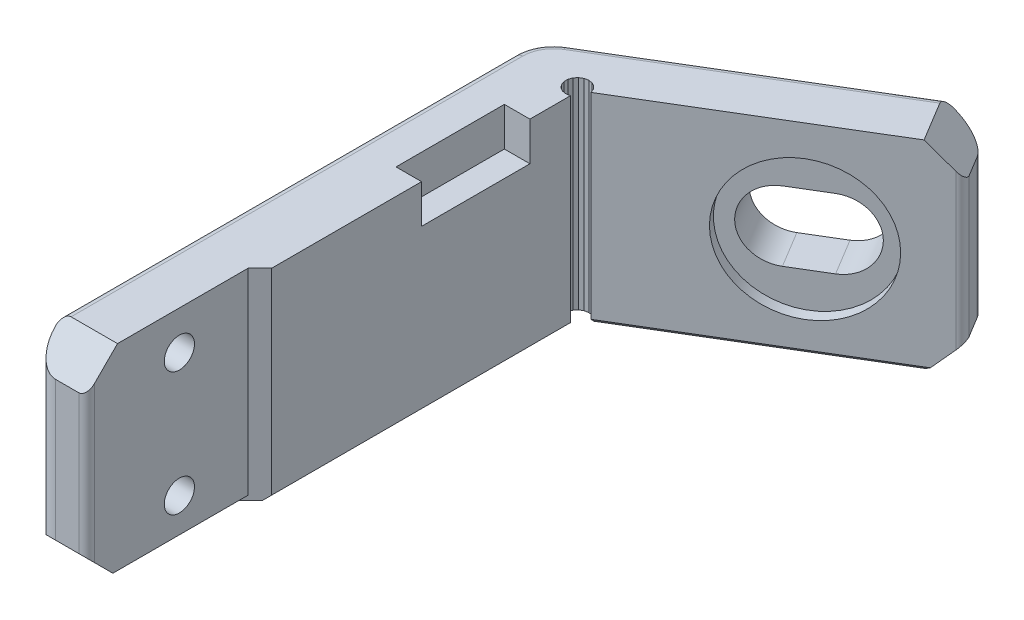
SolidWorks part; units mm, degrees
ref_plane "Front Plane" through (0, 0, 0) normal (0, 0, 1) x (1, 0, 0)
ref_plane "Top Plane" through (0, 0, 0) normal (0, 1, 0) x (1, 0, 0)
ref_plane "Right Plane" through (0, 0, 0) normal (1, 0, 0) x (0, 0, -1)
ref_plane "PY -20.700" through (0, -20.7, 0) normal (0, 1, 0) x (1, 0, 0)
sketch "leg and pad sketch" plane through (0, -20.7, 0) normal (0, 1, 0) x (1, 0, 0)
  line L0 (0.5513, 30.3327) -> (0.3673, 30.8194)
  line L1 (0.3673, 30.8194) -> (0.028, 31.2139)
  line L2 (0.028, 31.2139) -> (-0.4256, 31.4688)
  line L3 (-0.4256, 31.4688) -> (-0.939, 31.5534)
  line L4 (-0.939, 31.5534) -> (-1.4504, 31.4576)
  line L5 (-1.4504, 31.4576) -> (-1.8983, 31.1928)
  line L6 (-1.8983, 31.1928) -> (-2.2288, 30.7909)
  line L7 (-2.2288, 30.7909) -> (-2.4021, 30.3003)
  line L8 (-2.4021, 30.3003) -> (-2.3973, 29.78)
  line L9 (-2.3973, 29.78) -> (-2.2152, 29.2926)
  line L10 (-2.2152, 29.2926) -> (-1.8775, 28.8968)
  line L11 (-1.8775, 28.8968) -> (-1.4248, 28.6402)
  line L12 (-1.4248, 28.6402) -> (-0.9118, 28.5536)
  line L13 (-0.9118, 28.5536) -> (-0.4, 28.6475)
  line L14 (-0.4, 28.6475) -> (-0.4, -9.98)
  line L15 (-0.4, -9.98) -> (-1.92, -11.5)
  line L16 (-1.92, -11.5) -> (-1.92, -32.37)
  line L17 (-1.92, -32.37) -> (-8.92, -32.37)
  line L18 (-8.92, -32.37) -> (-8.92, 32.7926)
  line L19 (-8.92, 32.7926) -> (27.2048, 54.5947)
  line L20 (27.2048, 54.5947) -> (30.8218, 48.6015)
  line L21 (30.8218, 48.6015) -> (0.5513, 30.3327)
extrude "leg and pad" add sketch "leg and pad sketch" along normal mid plane 26
ref_plane "PX -1.350" through (-1.35, 0, 0) normal (1, 0, 0) x (0, 0, -1)
sketch "screw head relief sketch" plane through (-1.35, 0, 0) normal (1, 0, 0) x (0, 0, -1)
  line L0 (23.4, -12.7) -> (23.4, -6.7)
  line L1 (23.4, -6.7) -> (9.4, -6.7)
  line L2 (9.4, -6.7) -> (9.4, -12.7)
  line L3 (9.4, -12.7) -> (23.4, -12.7)
extrude "screw head relief" cut sketch "screw head relief sketch" against normal mid plane 4.7
sketch "insert flange relief sketch" plane through (0, -20.7, 0) normal (0, 1, 0) x (1, 0, 0)
  line L0 (18.3249, 39.8914) -> (17.0331, 42.0318)
  line L1 (17.0331, 42.0318) -> (9.3276, 37.3814)
  line L2 (9.3276, 37.3814) -> (10.6194, 35.241)
  line L3 (10.6194, 35.241) -> (18.3249, 39.8914)
revolve "insert flange relief" cut sketch "insert flange relief sketch" angle 360 about L0
sketch "M6 slot end 1 sketch" plane through (0, -20.7, 0) normal (0, 1, 0) x (1, 0, 0)
  line L0 (20.4653, 41.1832) -> (15.8149, 48.8886)
  line L1 (15.8149, 48.8886) -> (11.9621, 46.5634)
  line L2 (11.9621, 46.5634) -> (16.6125, 38.858)
  line L3 (16.6125, 38.858) -> (20.4653, 41.1832)
revolve "M6 slot end 1" cut sketch "M6 slot end 1 sketch" angle 360 about L0
sketch "M6 slot end 2 sketch" plane through (0, -20.7, 0) normal (0, 1, 0) x (1, 0, 0)
  line L0 (16.1845, 38.5996) -> (11.5341, 46.3051)
  line L1 (11.5341, 46.3051) -> (7.6813, 43.9799)
  line L2 (7.6813, 43.9799) -> (12.3317, 36.2744)
  line L3 (12.3317, 36.2744) -> (16.1845, 38.5996)
revolve "M6 slot end 2" cut sketch "M6 slot end 2 sketch" angle 360 about L0
sketch "M6 slot middle sketch" plane through (0, -20.7, 0) normal (0, 1, 0) x (1, 0, 0)
  line L0 (16.1845, 38.5996) -> (20.4653, 41.1832)
  line L1 (20.4653, 41.1832) -> (15.8149, 48.8886)
  line L2 (15.8149, 48.8886) -> (11.5341, 46.3051)
  line L3 (11.5341, 46.3051) -> (16.1845, 38.5996)
extrude "M6 slot middle" cut sketch "M6 slot middle sketch" against normal mid plane 9
ref_plane "PX -5.420" through (-5.42, 0, 0) normal (1, 0, 0) x (0, 0, -1)
sketch "screw holes sketch" plane through (-5.42, 0, 0) normal (1, 0, 0) x (0, 0, -1)
  circle A0 centre (-20.375, -28.7) radius 1.95
  circle A1 centre (-20.375, -12.7) radius 1.95
extrude "screw holes" cut sketch "screw holes sketch" against normal mid plane 9
chamfer "leg top corners" distance 4 angle 45 2 edges at (-5.42, -7.7, 32.37) (-5.42, -33.7, 32.37) tangent propagation no
chamfer "pad end corners" distance 4 angle 45 2 edges at (29.0133, -7.7, -51.5981) (29.0133, -33.7, -51.5981) tangent propagation no
fillet "outside of the bend" radius 5 1 edges at (-8.92, -20.7, -32.7926) tangent propagation no
fillet "leg top outer edge" radius 3 1 edges at (-8.92, -20.7, 32.37) tangent propagation no
fillet "pad end outer edge" radius 3 1 edges at (27.2048, -20.7, -54.5947) tangent propagation no
fillet "leg top inner edge" radius 1 1 edges at (-1.92, -20.7, 32.37) tangent propagation no
fillet "pad end inner edge" radius 1 1 edges at (30.8218, -20.7, -48.6015) tangent propagation no
chamfer "bed face chamfer" distance 0.6 angle 45 6 edges at (13.9742, -33.7, -38.4337) (8.6383, -33.7, -43.3894) (-1.92, -33.7, 19.935) (-0.4, -33.7, -9.3337) (-8.2742, -33.7, -32.4281) (-8.92, -33.7, -0.8001)
fillet "top face edge" radius 1 3 edges at (8.6383, -7.7, -43.3894) (-8.2742, -7.7, -32.4281) (-8.92, -7.7, -0.8001)
equation "\"diffL\" = 608.8mm"
equation "\"diffW\" = 329.4mm"
equation "\"diffT\" = 2.9mm"
equation "\"chanSlotW\" = 12.9mm"
equation "\"chanSlotDepth\" = 11.13mm"
equation "\"chanFloor\" = 1.57mm"
equation "\"chanLeg\" = 12.7mm"
equation "\"lightL\" = 605mm"
equation "\"lightW\" = 331mm"
equation "\"lightH\" = 92mm"
equation "\"lightSideFlat\" = 30mm"
equation "\"lightSlopeLen\" = 33.1mm"
equation "\"lightWingDepth\" = 47.9mm"
equation "\"lightWingFlat\" = 90.2mm"
equation "\"lightChanW\" = 99.6mm"
equation "\"lightChanStand\" = 44.1mm"
equation "\"insFlangeD\" = 12.3mm"
equation "\"insFromEnd\" = 20.7mm"
equation "\"insUpSlope\" = 20.8mm"
equation "\"gaugeH\" = 10mm"
equation "\"gaugeStepLen\" = 14mm"
equation "\"gaugeStepW0\" = 13.1mm"
equation "\"gaugeStepDW\" = 0.2mm"
equation "\"gaugeSteps\" = 5mm"
equation "\"gaugeHandleLen\" = 30mm"
equation "\"gaugeHandleW\" = 24mm"
equation "\"gaugeSlot0\" = 3mm"
equation "\"gaugeSlotD\" = 0.1mm"
equation "\"gaugeSlotDepth\" = 8mm"
equation "\"gap\" = 25.4mm"
equation "\"edgeL\" = 1mm"
equation "\"edgeW\" = 0.75mm"
equation "\"proud\" = 1.5mm"
equation "\"seatClr\" = 0.15mm"
equation "\"tongueClrZ\" = 0.1mm"
equation "\"tongueClrX\" = 0.25mm"
equation "\"tongueLen\" = 30mm"
equation "\"armSide\" = 45mm"
equation "\"armEnd\" = 20mm"
equation "\"cornerCham\" = 3mm"
equation "\"brkW\" = 26mm"
equation "\"brkT\" = 7mm"
equation "\"brkSeatClr\" = 0.2mm"
equation "\"brkScrewSpan\" = 16mm"
equation "\"pilotD\" = 2.7mm"
equation "\"pilotDepth\" = 10mm"
equation "\"screwClrD\" = 3.9mm"
equation "\"jogBelow\" = 4mm"
equation "\"padT\" = 7mm"
equation "\"padLen\" = 31mm"
equation "\"m6Clr\" = 7mm"
equation "\"m6Slot\" = 3mm"
equation "\"flangeRelD\" = 17mm"
equation "\"flangeRelDepth\" = 1.5mm"
equation "\"relLen\" = 7mm"
equation "\"relDepth\" = 4mm"
equation "\"relLand\" = 2mm"
equation "\"knockN\" = 100mm"
equation "\"petgcfE\" = 3000mm"
equation "\"mockExtent\" = 110mm"
equation "\"relZnear\" = 9.4mm"
equation "\"relZfar\" = 23.4mm"
equation "\"headD\" = 8mm"
equation "\"headH\" = 2.5mm"
equation "\"headFromEnd\" = 6.8mm"
equation "\"headBack\" = 16.4mm"
equation "\"sideClr\" = 0.4mm"
equation "\"cornerRelR\" = 1.5mm"
equation "\"cornerRelBack\" = 0.6mm"
equation "\"endHeadH\" = 2.8mm"
equation "\"footClr\" = 1.2mm"
equation "\"footEndClr\" = 3.5mm"
equation "\"footLift\" = 6mm"
equation "\"footBlockClr\" = 0.5mm"
equation "\"footBack\" = 50mm"
equation "\"footFwd\" = 10mm"
equation "\"footBraceEnd\" = 3mm"
equation "\"footLoadN\" = 25mm"
equation "\"spacerLen\" = 60mm"
equation "\"spacerShort\" = 0.5mm"
equation "\"spacerCham\" = 0.8mm"
equation "\"spacerPerSide\" = 3mm"
equation "\"spacerPerEnd\" = 1mm"
equation "\"toolR\" = 9mm"
equation "\"visR\" = 4mm"
equation "\"edgeR\" = 1mm"
equation "\"bendOutR\" = 5mm"
equation "\"insideR\" = 2.5mm"
equation "\"footCornerR\" = 10mm"
equation "\"footFrontR\" = 8mm"
equation "\"braceKinkR\" = 12mm"
equation "\"bedCham\" = 1mm"
equation "\"bedChamSmall\" = 0.6mm"
equation "\"soleTopR\" = 2mm"
equation "\"cornerR\" = 6mm"
equation "\"rimInR\" = 1mm"
equation "\"insFlangeH\" = 1mm"
